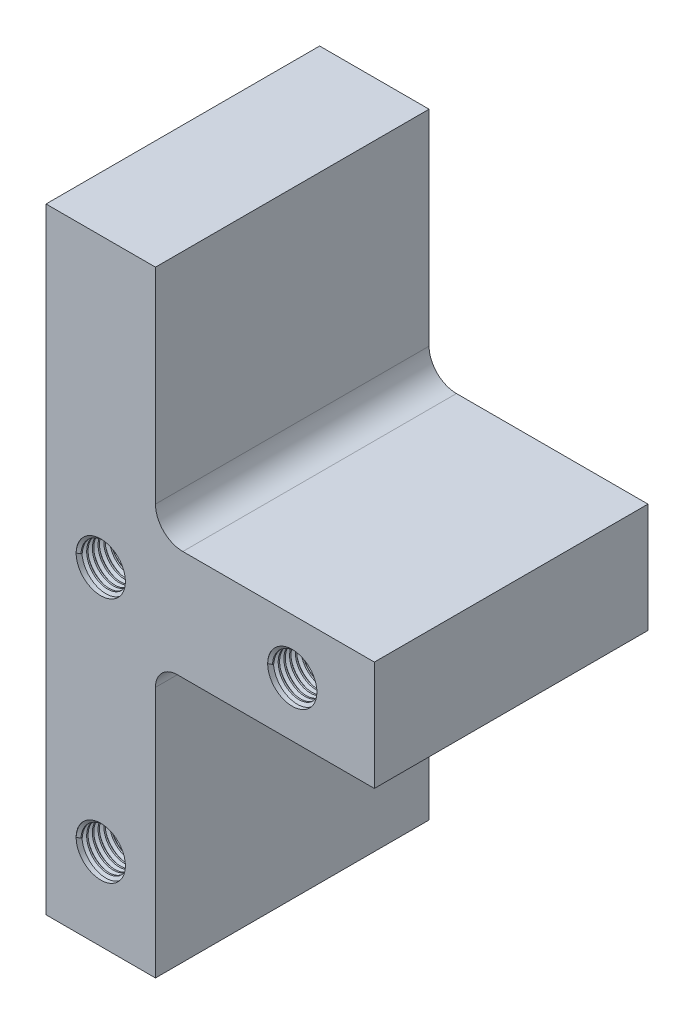
SolidWorks part; units mm, degrees
ref_plane "Front Plane" through (0, 0, 0) normal (0, 0, 1) x (1, 0, 0)
ref_plane "Top Plane" through (0, 0, 0) normal (0, 1, 0) x (1, 0, 0)
ref_plane "Right Plane" through (0, 0, 0) normal (1, 0, 0) x (0, 0, -1)
sketch "Sketch1" plane through (0, 0, 0) normal (0, 0, 1) x (1, 0, 0)
  line L0 (0, 0) -> (0, 35.56)
  line L2 (30.48, 35.56) -> (30.48, 25.4)
  line L3 (30.48, 25.4) -> (12.192, 25.4)
  line L4 (10.16, 23.368) -> (10.16, 0)
  line L5 (10.16, 0) -> (0, 0)
  line L6 (5.08, 0) -> (5.08, 7.62) construction
  line L7 (0, 35.56) -> (0, 57.15)
  line L8 (0, 57.15) -> (10.16, 57.15)
  line L9 (10.16, 57.15) -> (10.16, 38.1)
  line L10 (12.7, 35.56) -> (30.48, 35.56)
  circle A0 centre (5.08, 30.48) radius 2.286
  circle A1 centre (5.08, 7.62) radius 2.286
  circle A2 centre (22.86, 30.48) radius 2.286
  arc A3 (12.192, 25.4) -> (10.16, 23.368) centre (12.192, 23.368) ccw
  arc A4 (10.16, 38.1) -> (12.7, 35.56) centre (12.7, 38.1) ccw
  point P20 (10.16, 25.4)
  dimension "D1" = 4.572
  dimension "D2" = 5.08
  dimension "D8" = 2.032
  dimension "D11" = 2.54
  dimension "D9" = 4.572
  dimension "D3" = 7.62
  dimension "D4" = 30.48
  dimension "D5" = 22.86
  dimension "D6" = 10.16
  dimension "D7" = 17.78
  dimension "D10" = 57.15
  dimension "D12" = 23.368
extrude "Boss-Extrude1" add sketch "Sketch1" along normal blind 25.4
thread "Thread1" pitch 0.5292 method extrude profile "Thread Profile1" start angle 0, offset 0, length 14.732, pitch 0.5292, diameter 4.572
ref_plane "Plane1" through (2.794, 7.62, 25.4) normal (0, -1, 0) x (-1, 0, 0)
sketch "Thread Profile1" plane through (2.794, 7.62, 25.4) normal (0, -1, 0) x (-1, 0, 0)
  line L0 (0, 0) -> (0, 0.5292) construction
  line L11 (0, 0) -> (0, 0.463)
  line L12 (0, 0.463) -> (-0.2864, 0.2977)
  line L13 (-0.2864, 0.2977) -> (-0.2864, 0.1654)
  line L15 (-0.2864, 0.1654) -> (0, 0)
  line L17 (-0.2864, 0.2315) -> (0, 0.2315) construction
  point P2 (0, 0)
  dimension "Pitch" = 0.5292
  dimension "Profile_Angle" = 60
  dimension "Profile_Land" = 0.1323
  dimension "Profile_Height" = 0.2864
thread "Thread2" pitch 0.5292 method extrude profile "Thread Profile2" start angle 0, offset 0, length 14.732, pitch 0.5292, diameter 4.572
ref_plane "Plane2" through (2.794, 30.48, 25.4) normal (0, -1, 0) x (-1, 0, 0)
sketch "Thread Profile2" plane through (2.794, 30.48, 25.4) normal (0, -1, 0) x (-1, 0, 0)
  line L0 (0, 0) -> (0, 0.5292) construction
  line L11 (0, 0) -> (0, 0.463)
  line L12 (0, 0.463) -> (-0.2864, 0.2977)
  line L13 (-0.2864, 0.2977) -> (-0.2864, 0.1654)
  line L15 (-0.2864, 0.1654) -> (0, 0)
  line L17 (-0.2864, 0.2315) -> (0, 0.2315) construction
  point P2 (0, 0)
  dimension "Pitch" = 0.5292
  dimension "Profile_Angle" = 60
  dimension "Profile_Land" = 0.1323
  dimension "Profile_Height" = 0.2864
thread "Thread3" pitch 0.5292 method extrude profile "Thread Profile3" start angle 0, offset 0, length 14.732, pitch 0.5292, diameter 4.572
ref_plane "Plane3" through (20.574, 30.48, 25.4) normal (0, -1, 0) x (-1, 0, 0)
sketch "Thread Profile3" plane through (20.574, 30.48, 25.4) normal (0, -1, 0) x (-1, 0, 0)
  line L0 (0, 0) -> (0, 0.5292) construction
  line L11 (0, 0) -> (0, 0.463)
  line L12 (0, 0.463) -> (-0.2864, 0.2977)
  line L13 (-0.2864, 0.2977) -> (-0.2864, 0.1654)
  line L15 (-0.2864, 0.1654) -> (0, 0)
  line L17 (-0.2864, 0.2315) -> (0, 0.2315) construction
  point P2 (0, 0)
  dimension "Pitch" = 0.5292
  dimension "Profile_Angle" = 60
  dimension "Profile_Land" = 0.1323
  dimension "Profile_Height" = 0.2864
